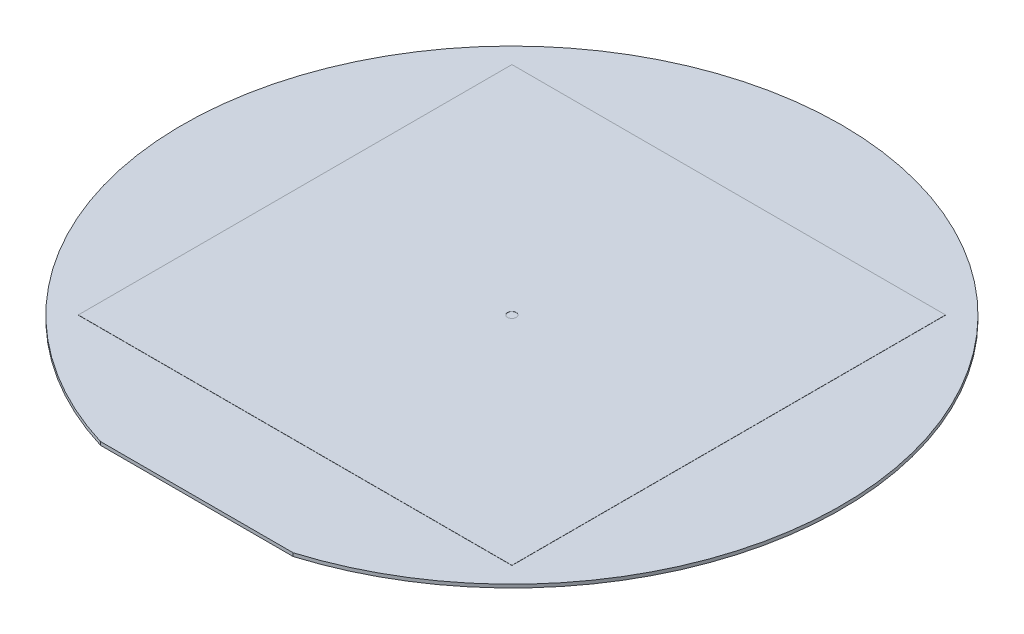
SolidWorks part; units mm, degrees
ref_plane "Front Plane" through (0, 0, 0) normal (0, 0, 1) x (1, 0, 0)
ref_plane "Top Plane" through (0, 0, 0) normal (0, 1, 0) x (1, 0, 0)
ref_plane "Right Plane" through (0, 0, 0) normal (1, 0, 0) x (0, 0, -1)
sketch "Sketch1" plane through (0, 0, 0) normal (0, 1, 0) x (1, 0, 0)
  line L1 (-25, 25) -> (25, 25)
  line L2 (-25, 25) -> (-25, -25)
  line L3 (-25, -25) -> (25, -25)
  line L4 (25, 25) -> (25, -25)
  line L5 (-25, 25) -> (25, -25) construction
  line L6 (-25, -25) -> (25, 25) construction
  circle A0 centre (0, 0) radius 0.5
  point P0 (0, 0)
  dimension "D2" = 1
  dimension "D1" = 50
extrude "Boss-Extrude1" add sketch "Sketch1" along normal blind 0.4
sketch "Sketch2" plane through (0, 0.4, 0) normal (0, 1, 0) x (1, 0, 0)
  line L0 (0, 25) -> (0, -25) construction
  line L1 (25, 25) -> (-25, 25) construction
  line L2 (-25, -25) -> (25, -25) construction
  line L3 (-25, 0) -> (25, 0) construction
  line L4 (-25, 25) -> (-25, -25) construction
  line L5 (25, -25) -> (25, 25) construction
sketch "Sketch3" plane through (0, 0, 0) normal (0, 1, 0) x (1, 0, 0)
  line L0 (-11.11, -36.3396) -> (11.11, -36.3396)
  circle A0 centre (0, 0) radius 38
  point P5 (0, -36.3396)
  dimension "D1" = 76
  dimension "D2" = 22.22
extrude "Boss-Extrude2" add sketch "Sketch3" along normal blind 0.381 contours L0 A0 region at (0, 0, -0.2026)
